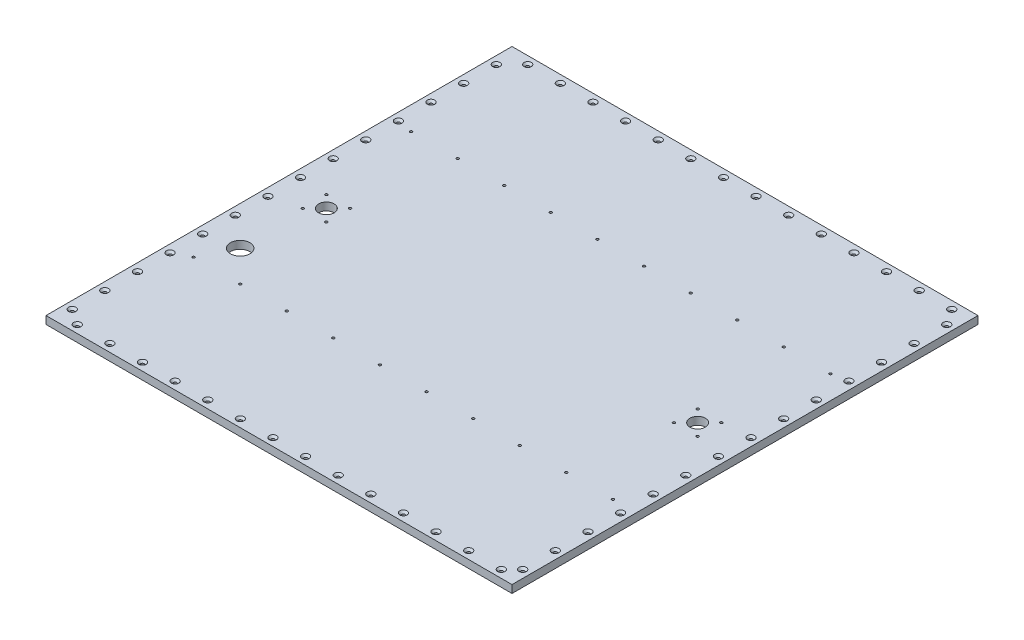
SolidWorks part; units mm, degrees
ref_plane "Płaszczyzna przednia" through (0, 0, 0) normal (0, 0, 1) x (1, 0, 0)
ref_plane "Płaszczyzna górna" through (0, 0, 0) normal (0, 1, 0) x (1, 0, 0)
ref_plane "Płaszczyzna prawa" through (0, 0, 0) normal (1, 0, 0) x (0, 0, -1)
sketch "Sketch1" plane through (0, 0, 0) normal (0, 1, 0) x (1, 0, 0)
  line L1 (0, 0) -> (600, 0)
  line L2 (0, 0) -> (0, 600)
  line L3 (0, 600) -> (600, 600)
  line L4 (600, 0) -> (600, 600)
  line L5 (0, 0) -> (600, 600) construction
  line L6 (0, 600) -> (600, 0) construction
  point P4 (300, 300)
  dimension "D1" = 600
  dimension "D2" = 600
extrude "Boss-Extrude1" add sketch "Sketch1" along normal blind 10
hole_wizard "CSK for M4 Flat Head Machine Screw1" positions "Sketch2" profile "Sketch3" countersink size "M4" standard "ANSI Metric" end condition through all
sketch "Sketch2" plane through (0, 10, 0) normal (0, 1, 0) x (1, 0, 0)
  line L0 (600, 600) -> (0, 600) construction
  line L1 (0, 600) -> (0, 0) construction
  point P0 (10, 569.75)
  point P2 (30.25, 590)
  point P20 (72.25, 590)
  point P21 (114.25, 590)
  point P22 (156.25, 590)
  point P23 (198.25, 590)
  point P24 (240.25, 590)
  point P25 (282.25, 590)
  point P26 (324.25, 590)
  point P27 (366.25, 590)
  point P28 (408.25, 590)
  point P29 (450.25, 590)
  point P30 (492.25, 590)
  point P31 (534.25, 590)
  point P32 (576.25, 590)
  point P33 (72.25, 10)
  point P34 (114.25, 10)
  point P35 (156.25, 10)
  point P36 (198.25, 10)
  point P37 (240.25, 10)
  point P38 (282.25, 10)
  point P39 (324.25, 10)
  point P40 (366.25, 10)
  point P41 (408.25, 10)
  point P42 (450.25, 10)
  point P43 (492.25, 10)
  point P44 (534.25, 10)
  point P45 (576.25, 10)
  point P46 (30.25, 10)
  point P53 (590, 569.75)
  point P54 (590, 527.75)
  point P55 (590, 485.75)
  point P56 (590, 443.75)
  point P57 (590, 401.75)
  point P58 (590, 359.75)
  point P59 (590, 317.75)
  point P60 (590, 275.75)
  point P61 (590, 233.75)
  point P62 (590, 191.75)
  point P63 (590, 149.75)
  point P64 (590, 107.75)
  point P65 (590, 65.75)
  point P66 (590, 23.75)
  point P67 (10, 527.75)
  point P68 (10, 485.75)
  point P69 (10, 443.75)
  point P70 (10, 401.75)
  point P71 (10, 359.75)
  point P72 (10, 317.75)
  point P73 (10, 275.75)
  point P74 (10, 233.75)
  point P75 (10, 191.75)
  point P76 (10, 149.75)
  point P77 (10, 107.75)
  point P78 (10, 65.75)
  point P79 (10, 23.75)
  dimension "D1" = 30.25
  dimension "D2" = 10
  dimension "D3" = 10
  dimension "D4" = 30.25
  dimension "D5" = 14
  dimension "D6" = 2
  dimension "D7" = 2
  dimension "D8" = 14
sketch "Sketch3" plane through (10, 10, -569.75) normal (1, 0, 0) x (0, 0, 1)
  line L0 (0, 0) -> (0, 10)
  line L1 (0, 10) -> (2.15, 10)
  line L2 (2.15, 10) -> (2.15, 2.55)
  line L3 (2.15, 2.55) -> (4.7, 0)
  line L5 (4.7, 0) -> (0, 0)
  line L6 (-2.15, 2.55) -> (-4.7, 0) construction
  line L11 (0, -6.35) -> (0, 107.95) construction
  dimension "Thru Hole Dia." = 4.3
  dimension "Thru Hole Depth" = 10
  dimension "Near C'Sink Dia." = 9.4
  dimension "Near C'Sink Angle" = 90
hole_wizard "CSK for M3 Flat Head Machine Screw1" positions "Sketch4" profile "Sketch6" countersink size "M3" standard "ANSI Metric" end condition through all
sketch "Sketch4" plane through (0, 0, 0) normal (0, -1, 0) x (-1, 0, 0)
  line L0 (-600, 0) -> (-600, 600) construction
  line L1 (0, 0) -> (-600, 0) construction
  line L2 (-600, 600) -> (0, 600) construction
  point P0 (-570, 160)
  point P2 (-570, 440)
  point P16 (-510, 160)
  point P17 (-510, 440)
  point P18 (-450, 160)
  point P19 (-450, 440)
  point P20 (-390, 160)
  point P21 (-390, 440)
  point P22 (-330, 160)
  point P23 (-330, 440)
  point P24 (-270, 160)
  point P25 (-270, 440)
  point P26 (-210, 160)
  point P27 (-210, 440)
  point P28 (-150, 160)
  point P29 (-150, 440)
  point P30 (-90, 160)
  point P31 (-90, 440)
  point P32 (-30, 160)
  point P33 (-30, 440)
  dimension "D1" = 30
  dimension "D2" = 160
  dimension "D3" = 30
  dimension "D4" = 160
  dimension "D5" = 10
sketch "Sketch6" plane through (570, 0, -160) normal (1, 0, 0) x (0, 0, -1)
  line L0 (0, 0) -> (0, 10)
  line L1 (0, 10) -> (1.6, 10)
  line L2 (1.6, 10) -> (1.6, 1.55)
  line L3 (1.6, 1.55) -> (3.15, 0)
  line L5 (3.15, 0) -> (0, 0)
  line L6 (-1.6, 1.55) -> (-3.15, 0) construction
  line L11 (0, -6.35) -> (0, 107.95) construction
  dimension "Thru Hole Dia." = 3.2
  dimension "Thru Hole Depth" = 10
  dimension "Near C'Sink Dia." = 6.3
  dimension "Near C'Sink Angle" = 90
sketch "Sketch7" plane through (0, 0, 0) normal (0, -1, 0) x (-1, 0, 0)
  line L0 (0, 600) -> (0, 0) construction
  line L1 (-600, 600) -> (0, 600) construction
  line L2 (-600, 0) -> (-600, 600) construction
  circle A0 centre (-61, 300) radius 10
  circle A1 centre (-539, 300) radius 10
  dimension "D2" = 20
  dimension "D3" = 300
  dimension "D4" = 20
  dimension "D5" = 61
  dimension "D6" = 300
  dimension "60" = 61
extrude "Cut-Extrude1" cut sketch "Sketch7" against normal blind 10
hole_wizard "CSK for M3 Flat Head Machine Screw2" positions "Sketch8" profile "Sketch9" countersink size "M3" standard "ANSI Metric" end condition through all
sketch "Sketch8" plane through (0, 0, 0) normal (0, -1, 0) x (-1, 0, 0)
  line L1 (0, 600) -> (0, 0) construction
  line L2 (-20, 600) -> (-580, 600) construction
  point P0 (-45.75, 315.25)
  point P2 (-76.25, 315.25)
  point P4 (-76.25, 284.75)
  point P6 (-45.75, 284.75)
  dimension "D1" = 30.5
  dimension "D2" = 45.75
  dimension "D3" = 30.5
  dimension "D4" = 284.75
sketch "Sketch9" plane through (45.75, 0, -315.25) normal (1, 0, 0) x (0, 0, -1)
  line L0 (0, 0) -> (0, 10)
  line L1 (0, 10) -> (1.6, 10)
  line L2 (1.6, 10) -> (1.6, 1.55)
  line L3 (1.6, 1.55) -> (3.15, 0)
  line L5 (3.15, 0) -> (0, 0)
  line L6 (-1.6, 1.55) -> (-3.15, 0) construction
  line L11 (0, -6.35) -> (0, 107.95) construction
  dimension "Thru Hole Dia." = 3.2
  dimension "Thru Hole Depth" = 10
  dimension "Near C'Sink Dia." = 6.3
  dimension "Near C'Sink Angle" = 90
hole_wizard "CSK for M3 Flat Head Machine Screw3" positions "Sketch10" profile "Sketch11" countersink size "M3" standard "ANSI Metric" end condition through all
sketch "Sketch10" plane through (0, 0, 0) normal (0, -1, 0) x (-1, 0, 0)
  line L0 (-600, 0) -> (-600, 600) construction
  line L3 (-20, 600) -> (-580, 600) construction
  point P0 (-523.75, 315.25)
  point P2 (-554.25, 315.25)
  point P4 (-554.25, 284.75)
  point P6 (-523.75, 284.75)
  dimension "D1" = 45.75
  dimension "D2" = 284.75
  dimension "D3" = 30.5
  dimension "D4" = 30.5
sketch "Sketch11" plane through (523.75, 0, -315.25) normal (1, 0, 0) x (0, 0, -1)
  line L0 (0, 0) -> (0, 10)
  line L1 (0, 10) -> (1.6, 10)
  line L2 (1.6, 10) -> (1.6, 1.55)
  line L3 (1.6, 1.55) -> (3.15, 0)
  line L5 (3.15, 0) -> (0, 0)
  line L6 (-1.6, 1.55) -> (-3.15, 0) construction
  line L11 (0, -6.35) -> (0, 107.95) construction
  dimension "Thru Hole Dia." = 3.2
  dimension "Thru Hole Depth" = 10
  dimension "Near C'Sink Dia." = 6.3
  dimension "Near C'Sink Angle" = 90
hole_wizard "CSK for M3 Flat Head Machine Screw4" positions "Sketch12" profile "Sketch13" countersink size "M3" standard "ANSI Metric"
sketch "Sketch12" plane through (0, 0, 0) normal (0, -1, 0) x (-1, 0, 0)
  line L0 (-600, 580) -> (-600, 20) construction
  line L1 (-20, 0) -> (-580, 0) construction
  point P0 (-549.5, 118.5)
  point P2 (-549.5, 68.8)
  point P4 (-397.5, 118.5)
  point P6 (-397.5, 68.8)
  dimension "D1" = 50.5
  dimension "D2" = 118.5
  dimension "D3" = 49.7
  dimension "D4" = 152
sketch "Sketch13" plane through (549.5, 0, -118.5) normal (1, 0, 0) x (0, 0, -1)
  line L0 (0, 0) -> (0, 6.9614)
  line L1 (0, 6.9614) -> (1.6, 6)
  line L2 (1.6, 6) -> (1.6, 1.55)
  line L3 (1.6, 1.55) -> (3.15, 0)
  line L5 (3.15, 0) -> (0, 0)
  line L6 (-1.6, 1.55) -> (-3.15, 0) construction
  line L10 (0, 6.9614) -> (-1.6, 6) construction
  line L11 (0, -6.35) -> (0, 107.95) construction
  dimension "Hole Dia." = 3.2
  dimension "Hole Depth" = 6
  dimension "Near C'Sink Dia." = 6.3
  dimension "Near C'Sink Angle" = 90
  dimension "Drill Angle" = 118
sketch "Sketch14" plane through (0, 0, 0) normal (0, -1, 0) x (1, 0, 0)
  line L0 (0, 0) -> (600, 0) construction
  line L1 (600, -580) -> (600, -20) construction
  circle A0 centre (425, -42) radius 4
  dimension "D1" = 42
  dimension "D2" = 175
  dimension "D3" = 8
extrude "Cut-Extrude2" cut sketch "Sketch14" against normal blind 5
sketch "Sketch15" plane through (0, 0, 0) normal (0, -1, 0) x (-1, 0, 0)
  line L0 (-20, 0) -> (-580, 0) construction
  line L1 (0, 20) -> (0, 580) construction
  circle A0 centre (-175, 42) radius 4
  dimension "D1" = 42
  dimension "D2" = 8
  dimension "D3" = 175
extrude "Cut-Extrude3" cut sketch "Sketch15" against normal blind 5
sketch "Sketch16" plane through (0, 10, 0) normal (0, 1, 0) x (1, 0, 0)
  line L0 (0, 0) -> (0, 600) construction
  line L1 (0, 0) -> (600, 0) construction
  circle A0 centre (50, 200) radius 12.5
  dimension "D1" = 25
  dimension "D2" = 50
  dimension "D3" = 200
extrude "Cut-Extrude4" cut sketch "Sketch16" against normal blind 10
